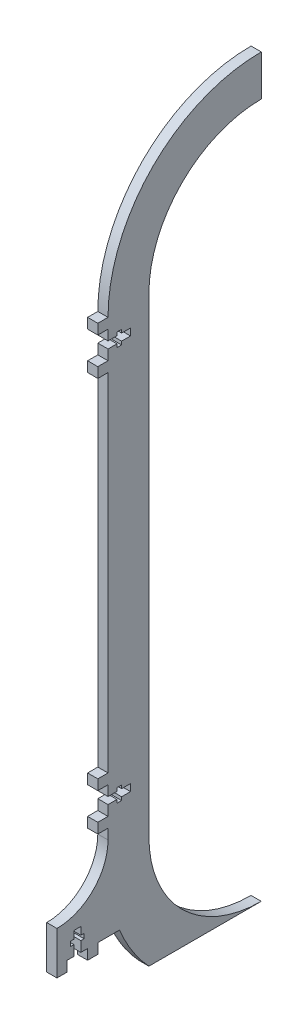
SolidWorks part; units mm, degrees
ref_plane "Front Plane" through (0, 0, 0) normal (0, 0, 1) x (1, 0, 0)
ref_plane "Top Plane" through (0, 0, 0) normal (0, 1, 0) x (1, 0, 0)
ref_plane "Right Plane" through (0, 0, 0) normal (1, 0, 0) x (0, 0, -1)
sketch "Elevator Ball Support Rail" plane through (0, 0, 0) normal (1, 0, 0) x (0, 0, -1)
  line L0 (69.85, 215.9) -> (69.85, 241.3)
  line L1 (-25.4, 146.05) -> (-31.75, 146.05)
  line L2 (69.85, -215.9) -> (0, -215.9)
  line L3 (-31.75, -187.325) -> (-18.2601, -187.325)
  line L4 (-38.1, -193.675) -> (-31.75, -193.675)
  line L5 (-38.1, -187.325) -> (-38.1, -193.675)
  line L6 (0, 146.05) -> (0, -146.05)
  line L7 (-25.4, -135.255) -> (-25.4, -187.325) construction
  line L8 (0, -146.05) -> (0, -215.9) construction
  line L9 (-31.75, -187.325) -> (-31.75, -193.675)
  line L10 (-50.8, -187.325) -> (-46.609, -187.325)
  line L11 (-25.4, 139.7) -> (-25.4, 133.35)
  line L12 (-57.15, -167.005) -> (-57.15, -193.675)
  line L13 (-57.15, -193.675) -> (-50.8, -193.675)
  line L14 (-42.291, -187.325) -> (-38.1, -187.325)
  line L15 (-50.8, -193.675) -> (-50.8, -187.325)
  line L16 (-42.291, -180.975) -> (-42.291, -187.325)
  line L17 (-42.291, -180.975) -> (-40.25, -180.975)
  line L18 (-40.25, -180.975) -> (-40.25, -178.075)
  line L19 (-42.291, -178.075) -> (-42.291, -173.355)
  line L20 (-42.291, -173.355) -> (-46.609, -173.355)
  line L21 (-40.25, -178.075) -> (-42.291, -178.075)
  line L22 (-48.65, -178.075) -> (-48.65, -180.975)
  line L23 (-48.65, -180.975) -> (-46.609, -180.975)
  line L24 (-46.609, -180.975) -> (-46.609, -187.325)
  line L25 (-46.609, -173.355) -> (-46.609, -178.075)
  line L26 (-46.609, -178.075) -> (-48.65, -178.075)
  line L27 (0, -187.325) -> (101.6, -187.325) construction
  line L28 (-31.75, 146.05) -> (-31.75, 139.7)
  line L29 (-31.75, 139.7) -> (-25.4, 139.7)
  line L30 (-25.4, 133.35) -> (-19.865, 133.35)
  line L31 (-19.865, 133.35) -> (-19.865, 135.391)
  line L32 (-19.865, 135.391) -> (-16.965, 135.391)
  line L33 (-16.965, 135.391) -> (-16.965, 133.35)
  line L34 (-16.965, 133.35) -> (-11.43, 133.35)
  line L35 (-11.43, 133.35) -> (-11.43, 129.032)
  line L36 (-11.43, 129.032) -> (-16.965, 129.032)
  line L37 (-16.965, 129.032) -> (-16.965, 126.991)
  line L38 (-16.965, 126.991) -> (-19.865, 126.991)
  line L39 (-19.865, 126.991) -> (-19.865, 129.032)
  line L40 (-19.865, 129.032) -> (-25.4, 129.032)
  line L41 (-25.4, 129.032) -> (-25.4, 122.682)
  line L42 (0, 0) -> (-25.4, 0) construction
  line L43 (-25.4, 122.682) -> (-31.75, 122.682)
  line L44 (-31.75, 122.682) -> (-31.75, 116.332)
  line L45 (-31.75, 116.332) -> (-25.4, 116.332)
  line L46 (-25.4, 116.332) -> (-25.4, -99.187)
  line L47 (-25.4, -99.187) -> (-31.75, -99.187)
  line L48 (-25.4, -105.537) -> (-25.4, -111.887)
  line L49 (-31.75, -99.187) -> (-31.75, -105.537)
  line L50 (-31.75, -105.537) -> (-25.4, -105.537)
  line L51 (-25.4, -111.887) -> (-19.865, -111.887)
  line L52 (-19.865, -111.887) -> (-19.865, -109.846)
  line L53 (-19.865, -109.846) -> (-16.965, -109.846)
  line L54 (-16.965, -109.846) -> (-16.965, -111.887)
  line L55 (-16.965, -111.887) -> (-11.43, -111.887)
  line L56 (-11.43, -111.887) -> (-11.43, -116.205)
  line L57 (-11.43, -116.205) -> (-16.965, -116.205)
  line L58 (-16.965, -116.205) -> (-16.965, -118.246)
  line L59 (-16.965, -118.246) -> (-19.865, -118.246)
  line L60 (-19.865, -118.246) -> (-19.865, -116.205)
  line L61 (-19.865, -116.205) -> (-25.4, -116.205)
  line L62 (-25.4, -116.205) -> (-25.4, -122.555)
  line L63 (-25.4, -122.555) -> (-31.75, -122.555)
  line L64 (-31.75, -122.555) -> (-31.75, -128.905)
  line L65 (-25.4, -135.255) -> (-25.4, -128.905)
  line L68 (-25.4, -128.905) -> (-31.75, -128.905)
  arc A0 (0, 146.05) -> (69.85, 215.9) centre (69.85, 146.05) cw
  arc A1 (69.85, 241.3) -> (-25.4, 146.05) centre (69.85, 146.05) ccw
  arc A2 (0, -146.05) -> (69.85, -215.9) centre (69.85, -146.05) ccw
  arc A3 (-18.2601, -187.325) -> (0, -215.9) centre (69.85, -151.1425) ccw
  arc A4 (-57.15, -167.005) -> (-25.4, -135.255) centre (-57.15, -135.255) ccw
  point P4 (0, 0)
  dimension "D5" = 25.4
  dimension "D4" = 69.85
  dimension "D7" = 69.85
  dimension "D8" = 6.35
  dimension "D14" = 12.7
  dimension "D13" = 6.35
  dimension "D6" = 6.35
  dimension "D3" = 292.1
  dimension "D9" = 22.225
  dimension "D10" = 6.35
  dimension "D11" = 6.35
  dimension "D12" = 6.35
  dimension "D15" = 2.9
  dimension "D16" = 8.4
  dimension "D17" = 6.35
  dimension "D18" = 4.318
  dimension "D19" = 13.97
  dimension "D20" = 41.275
  dimension "D21" = 6.35
  dimension "D22" = 6.35
  dimension "D23" = 4.318
  dimension "D24" = 2.9
  dimension "D25" = 8.4
  dimension "D26" = 6.35
  dimension "D27" = 13.97
  dimension "D28" = 6.35
  dimension "D29" = 4.318
  dimension "D30" = 2.9
  dimension "D31" = 13.97
  dimension "D32" = 6.35
  dimension "D33" = 8.4
  dimension "D34" = 6.35
  dimension "D35" = 6.35
  dimension "D36" = 25.4
extrude "Boss-Extrude2" add sketch "Elevator Ball Support Rail" along normal blind 6.35 contours A4 L12 L13 L15 L10 L24 L23 L22 L26 L25 L20 L19 L21 L18 L17 L16 L14 L5 L4 L9 L3 A3 L2 A2 L6 A0 L0 A1 L1 L28 L29 L11 L30 L31 L32 L33 L34 L35 L36 L37 L38 L39 L40 L41 L43 L44 L45 L46 L47 L49 L50 region at (0, 4.4022, 5.254)
equation "\"Ball Diameter\"= 1.75in"
equation "\"Pulley Diameter\" = 1in"
equation "\"Reactor Height\" = 14in"
equation "\"Sheet Thickness\"= 0.25in"
equation "\"Screw Diameter\"= .17in"
equation "\"Robot Diameter\"= 14in"
equation "\"Castor Screw Diameter\"= 0.22in"
equation "\"Wheel Diameter\" = 4in"
equation "\"Nut Diameter\" = 8.4mm"
equation "\"Nut Height\" = 2.9mm"
equation "\"Screw Height\" = 0.55in"
equation "\"D11@Elevator Ball Support Rail\"=\"Sheet Thickness\""
equation "\"Elevator Height\" = 11.5in"
equation "\"D12@Elevator Ball Support Rail\"=\"Sheet Thickness\""
equation "\"D7@Elevator Ball Support Rail\"=\"Elevator Clearance from Axis\""
equation "\"D10@Elevator Ball Support Rail\"=\"Sheet Thickness\""
equation "\"D13@Elevator Ball Support Rail\"=\"Sheet Thickness\""
equation "\"D1@T-Slot\" = \"Screw Diameter\""
equation "\"D16@Elevator Ball Support Rail\"=\"Nut Diameter\""
equation "\"D15@Elevator Ball Support Rail\"=\"Nut Height\""
equation "\"D16@Elevator Ball Support Rail\" = \"Nut Diameter\""
equation "\"D9@Elevator Ball Support Rail\"=\"Ball Diameter\"/2"
equation "\"D1@Boss-Extrude2\"=\"Sheet Thickness\""
equation "\"D18@Elevator Ball Support Rail\"=\"Screw Diameter\""
equation "\"D19@Elevator Ball Support Rail\"=\"Screw Height\""
equation "\"D3@Elevator Ball Support Rail\"=\"Elevator Height\""
equation "\"Elevator Width\" = \"Ball Diameter\" + 0.25in"
equation "\"Elevator Bearing Diameter\" = sqr(2*(\"Sheet Thickness\"^2)) + 0.2in"
equation "\"Elevator Axle Endcap Diameter\" = \"Pulley Diameter\" + 0.25in"
equation "\"Elevator Axle Length\" = \"Elevator Width\" + 8*\"Sheet Thickness\""
equation "\"Elevator Clearance from Axis\" = (\"Pulley Diameter\"/2) + \"Ball Diameter\" + 0.5in"
equation "\"D4@Elevator Ball Support Rail\"=\"Elevator Clearance from Axis\""
equation "\"D21@Elevator Ball Support Rail\"=\"Sheet Thickness\""
equation "\"D22@Elevator Ball Support Rail\"=\"Sheet Thickness\""
equation "\"D23@Elevator Ball Support Rail\"=\"Screw Diameter\""
equation "\"D24@Elevator Ball Support Rail\"=\"Nut Height\""
equation "\"D25@Elevator Ball Support Rail\"=\"Nut Diameter\""
equation "\"D26@Elevator Ball Support Rail\"=\"Sheet Thickness\""
equation "\"D27@Elevator Ball Support Rail\"=\"Screw Height\""
equation "\"D32@Elevator Ball Support Rail\"=\"Sheet Thickness\""
equation "\"D33@Elevator Ball Support Rail\"=\"Nut Diameter\""
equation "\"D34@Elevator Ball Support Rail\"=\"Sheet Thickness\""
equation "\"D35@Elevator Ball Support Rail\"=\"Sheet Thickness\""
equation "\"D30@Elevator Ball Support Rail\"=\"Nut Height\""
equation "\"D28@Elevator Ball Support Rail\"=\"Sheet Thickness\""
equation "\"D29@Elevator Ball Support Rail\"=\"Screw Diameter\""
equation "\"D31@Elevator Ball Support Rail\"=\"Screw Height\""
